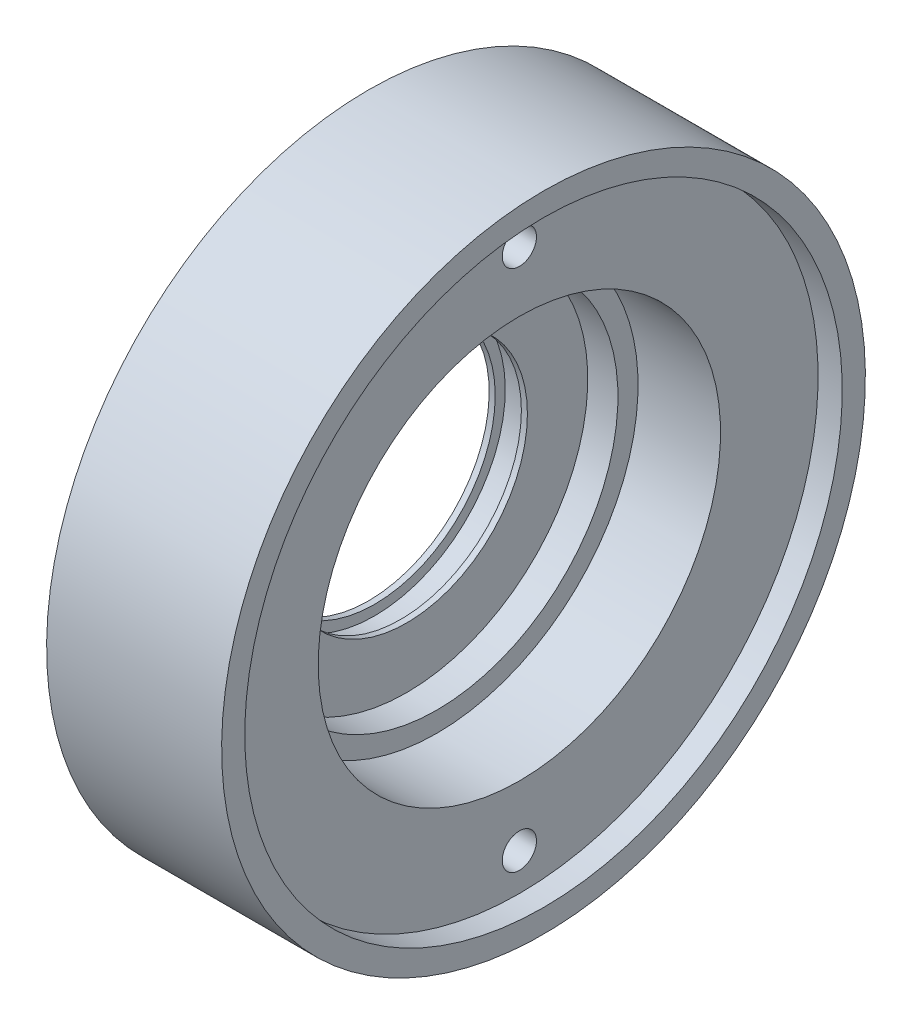
SolidWorks part; units mm, degrees
note: The reader was unsure of these and kept them because the rebuilt part matched: shared geometry of "Esquisse2<3>".
ref_plane "Plan de face" through (0, 0, 0) normal (0, 0, 1) x (1, 0, 0)
ref_plane "Plan de dessus" through (0, 0, 0) normal (0, 1, 0) x (1, 0, 0)
ref_plane "Plan de droite" through (0, 0, 0) normal (1, 0, 0) x (0, 0, -1)
sketch "Esquisse1" plane through (0, 0, 0) normal (0, 0, 1) x (1, 0, 0)
  line L0 (0, 0) -> (0, 160)
  line L1 (0, 160) -> (87, 160)
  line L2 (87, 160) -> (87, 0)
  line L3 (87, 0) -> (0, 0)
  dimension "D1" = 160
  dimension "D2" = 87
revolve "Révolution1" add sketch "Esquisse1" angle 360 about L3
sketch "Esquisse2" plane through (87, 0, 0) normal (1, 0, 0) x (0, 0, -1)
  circle A0 centre (0, 0) radius 148.5
  circle A1 centre (0, 0) radius 90
  circle A2 centre (0, 0) radius 100
  dimension "D1" = 297
  dimension "D2" = 180
  dimension "D3" = 200
extrude "Enlèv. mat.-Extru.1" cut sketch "Esquisse2" against normal blind 12 contours A0
extrude "Enlèv. mat.-Extru.2" cut sketch "Esquisse2<3>" against normal blind 53 contours A1 | A2
sketch "Esquisse2<3>" plane through (87, 0, 0) normal (1, 0, 0) x (0, 0, -1) same geometry as "Esquisse2"
sketch "Esquisse4" plane through (75, 0, 0) normal (1, 0, 0) x (0, 0, -1)
  circle A0 centre (0, 0) radius 90
  dimension "D1" = 180
extrude "Enlèv. mat.-Extru.3" cut sketch "Esquisse4" against normal blind 56
sketch "Esquisse10" plane through (0, 0, 0) normal (-1, 0, 0) x (0, 0, 1)
  circle A0 centre (0, 0) radius 60
  dimension "D1" = 120
extrude "Enlèv. mat.-Extru.4" cut sketch "Esquisse10" against normal blind 56
sketch "Esquisse11" plane through (0, 0, 0) normal (1, 0, 0) x (0, 0, -1)
  circle A0 centre (0, 0) radius 65
  dimension "D1" = 130
extrude "Enlèv. mat.-Extru.7" cut sketch "Esquisse11" along a picked direction on the side of the normal blind 13 from offset 3 contours A0
sketch "Esquisse14" plane through (0, 0, 0) normal (-1, 0, 0) x (0, 0, 1)
  line L0 (0, 0) -> (0, 130)
  line L1 (0, 0) -> (0, -130)
  circle A0 centre (0, 0) radius 130
  dimension "D1" = 260
hole_wizard "Perçage2" positions "Esquisse3D18" profile "Esquisse15" legacy
sketch3d "Esquisse3D18"
  point P0 (0, 130, 0)
  point P3 (0, -130, 0)
sketch "Esquisse15" plane through (0, 130, 0) normal (0, 1, 0) x (0, 0, 1)
  line L0 (0, 0) -> (0, 83)
  line L1 (0, 83) -> (8.5, 83)
  line L2 (8.5, 83) -> (8.5, 16)
  line L3 (8.5, 16) -> (12.5, 16)
  line L4 (12.5, 16) -> (12.5, 0)
  line L5 (12.5, 0) -> (0, 0)
  line L6 (0, 110) -> (0, -10) construction
  dimension "Diamètre" = 17
  dimension "Profondeur" = 83
  dimension "Diamètre chambrage" = 25
  dimension "Profondeur chambrage" = 16
